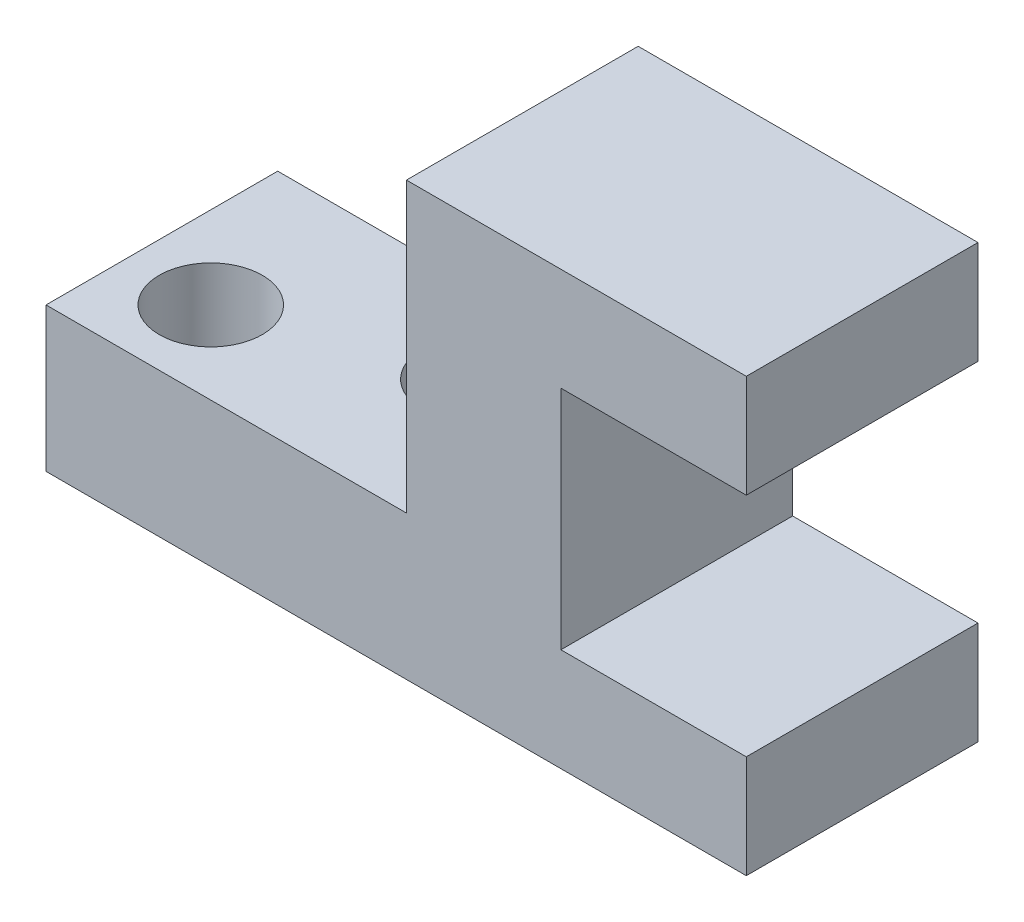
SolidWorks part; units mm, degrees
ref_plane "Front Plane" through (0, 0, 0) normal (0, 0, 1) x (1, 0, 0)
ref_plane "Top Plane" through (0, 0, 0) normal (0, 1, 0) x (1, 0, 0)
ref_plane "Right Plane" through (0, 0, 0) normal (1, 0, 0) x (0, 0, -1)
sketch "Sketch1" plane through (0, 0, 0) normal (0, 0, 1) x (1, 0, 0)
  line L0 (0, 0) -> (-13.6, 0)
  line L1 (-13.6, 0) -> (-13.6, 2.8)
  line L2 (-13.6, 2.8) -> (-6.6, 2.8)
  line L3 (-6.6, 2.8) -> (-6.6, 8.4)
  line L4 (-6.6, 8.4) -> (0, 8.4)
  line L5 (0, 8.4) -> (0, 6.4)
  line L6 (0, 6.4) -> (-3.6, 6.4)
  line L7 (-3.6, 6.4) -> (-3.6, 2)
  line L8 (-3.6, 2) -> (0, 2)
  line L9 (0, 2) -> (0, 0)
  dimension "D1" = 2
  dimension "D2" = 2
  dimension "D3" = 3
  dimension "D4" = 3.6
  dimension "D5" = 4.4
  dimension "D6" = 7
  dimension "D7" = 2.8
extrude "Boss-Extrude1" add sketch "Sketch1" along normal blind 4.5
sketch "Sketch2" plane through (0, 2.8, 0) normal (0, 1, 0) x (1, 0, 0)
  line L0 (-6.6, -4.5) -> (-13.6, -4.5) construction
  line L1 (-6.6, 0) -> (-13.6, 0) construction
  line L2 (-13.6, -4.5) -> (-13.6, 0) construction
  line L3 (-6.6, -4.5) -> (-6.6, 0) construction
  circle A0 centre (-8.2, -1.6) radius 1
  circle A1 centre (-12, -2.9) radius 1
  dimension "D1" = 2
  dimension "D2" = 2
  dimension "D3" = 1.6
  dimension "D4" = 1.6
  dimension "D5" = 1.6
  dimension "D6" = 1.6
extrude "Cut-Extrude1" cut sketch "Sketch2" against normal blind 10
